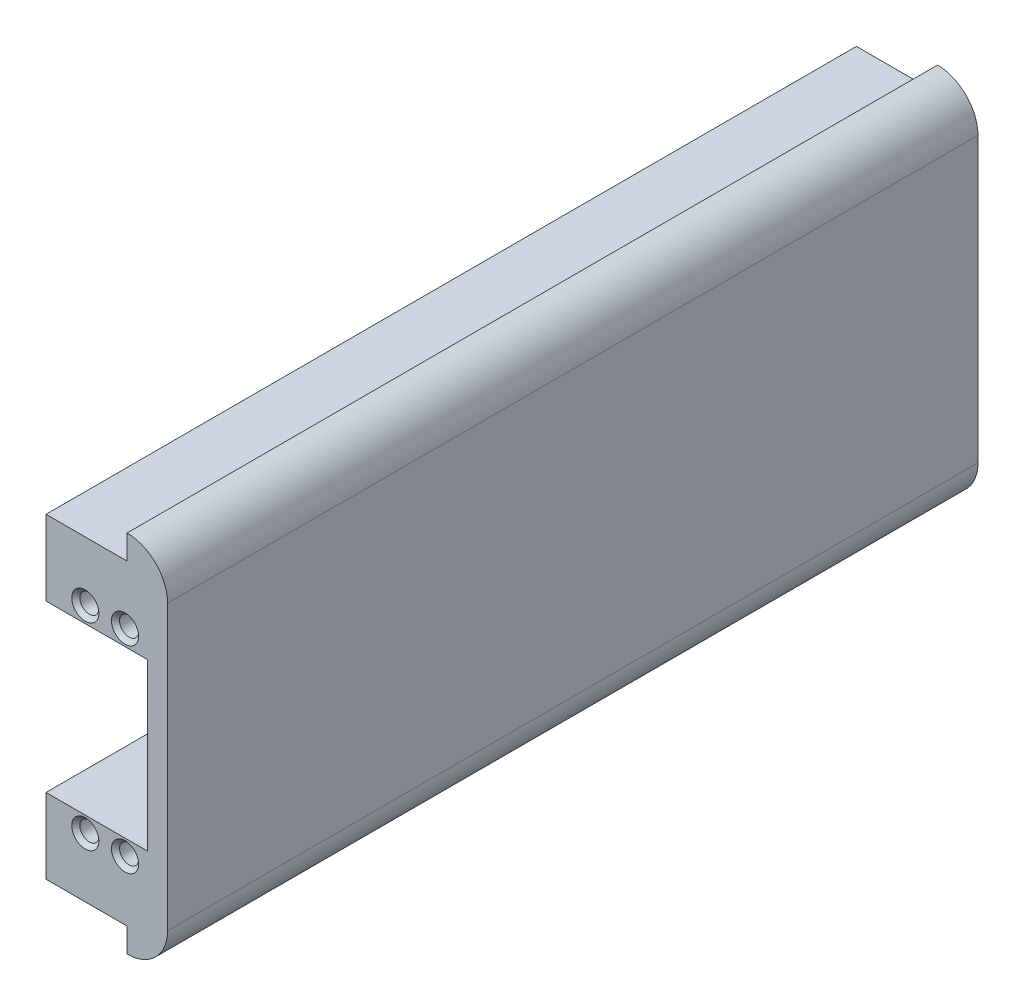
SolidWorks part; units mm, degrees
material "ABS"
ref_plane "Front Plane" through (0, 0, 0) normal (0, 0, 1) x (1, 0, 0)
ref_plane "Top Plane" through (0, 0, 0) normal (0, 1, 0) x (1, 0, 0)
ref_plane "Right Plane" through (0, 0, 0) normal (1, 0, 0) x (0, 0, -1)
sketch "Sketch1" plane through (0, 0, 0) normal (0, 0, 1) x (1, 0, 0)
  line L0 (-15, 45) -> (15, 45)
  line L1 (-15, 45) -> (15, 45) construction
  line L2 (-15, 45) -> (-15, -45) construction
  line L3 (-15, -45) -> (15, -45) construction
  line L4 (15, 45) -> (15, -45) construction
  line L5 (-15, 45) -> (15, -45) construction
  line L6 (-15, -45) -> (15, 45) construction
  line L7 (15, 45) -> (15, -45)
  line L8 (15, -45) -> (-15, -45)
  line L9 (-15, -45) -> (-15, -20.45)
  line L10 (-15, -20.45) -> (10, -20.45)
  line L11 (10, -20.45) -> (10, 20.45)
  line L12 (10, 20.45) -> (-15, 20.45)
  line L13 (-15, 20.45) -> (-15, 45)
  point P0 (0, 0)
  dimension "D1" = 90
  dimension "D2" = 30
  dimension "D3" = 40.9
  dimension "D5" = 5
extrude "Boss-Extrude1" add sketch "Sketch1" along normal blind 200
sketch "Sketch2" plane through (0, 0, 200) normal (0, 0, 1) x (1, 0, 0)
  line L0 (10, 20.45) -> (-10.8, 20.45) construction
  line L1 (-15, 20.45) -> (10, 20.45) construction
  line L2 (-0.4, 20.45) -> (-0.4, 24.34) construction
  line L3 (-0.4, 24.34) -> (4.5, 24.34) construction
  line L4 (10, 20.45) -> (10, -20.45) construction
  line L5 (10, 0) -> (15, 0) construction
  line L6 (15, -45) -> (15, 45) construction
  circle A0 centre (4.5, 24.34) radius 2.35
  circle A1 centre (-5.3, 24.34) radius 2.35
  circle A2 centre (-5.3, -24.34) radius 2.35
  circle A3 centre (4.5, -24.34) radius 2.35
  dimension "D4" = 4.7
  dimension "D1" = 20.8
  dimension "D2" = 3.89
  dimension "D3" = 4.9
extrude "Cut-Extrude1" cut sketch "Sketch2" against normal blind 8
sketch "Sketch3" plane through (0, 0, 0) normal (0, 0, -1) x (-1, 0, 0)
  line L0 (-10, 20.45) -> (10.8, 20.45) construction
  line L1 (15, 20.45) -> (-10, 20.45) construction
  line L2 (-10, 20.45) -> (-10, -20.45) construction
  line L3 (-10, 0) -> (-15, 0) construction
  line L4 (-15, -45) -> (-15, 45) construction
  line L5 (0.4, 20.45) -> (0.4, 24.34) construction
  line L6 (0.4, 24.34) -> (-4.5, 24.34) construction
  circle A0 centre (-4.5, 24.34) radius 2.35
  circle A1 centre (5.3, 24.34) radius 2.35
  circle A2 centre (5.3, -24.34) radius 2.35
  circle A3 centre (-4.5, -24.34) radius 2.35
  dimension "D4" = 4.7
  dimension "D1" = 20.8
  dimension "D2" = 3.89
  dimension "D3" = 4.9
extrude "Cut-Extrude2" cut sketch "Sketch3" against normal blind 8
chamfer "Chamfer1" distance 1 angle 45 8 edges at (-7.65, -24.34, 0) (6.85, -24.34, 0) (2.15, 24.34, 0) (-2.95, 24.34, 0) (2.15, -24.34, 200) (-2.95, -24.34, 200) (-7.65, 24.34, 200) (6.85, 24.34, 200)
sketch "Sketch4" plane through (0, 0, 200) normal (0, 0, 1) x (1, 0, 0)
  line L0 (0, 0) -> (15, 0) construction
  line L1 (-15, -45) -> (5, -45)
  line L2 (-15, -45) -> (-15, -39)
  line L3 (-15, -39) -> (5, -39)
  line L4 (5, -45) -> (5, -39)
  line L5 (15, -45) -> (15, 45) construction
  line L6 (-15, 39) -> (5, 39)
  line L7 (5, 45) -> (5, 39)
  line L8 (-15, 45) -> (5, 45)
  line L9 (-15, 45) -> (-15, 39)
  dimension "D1" = 6
  dimension "D2" = 20
extrude "Cut-Extrude3" cut sketch "Sketch4" against normal through all
fillet "Fillet1" radius 10 2 edges at (15, 45, 100) (15, -45, 100)
